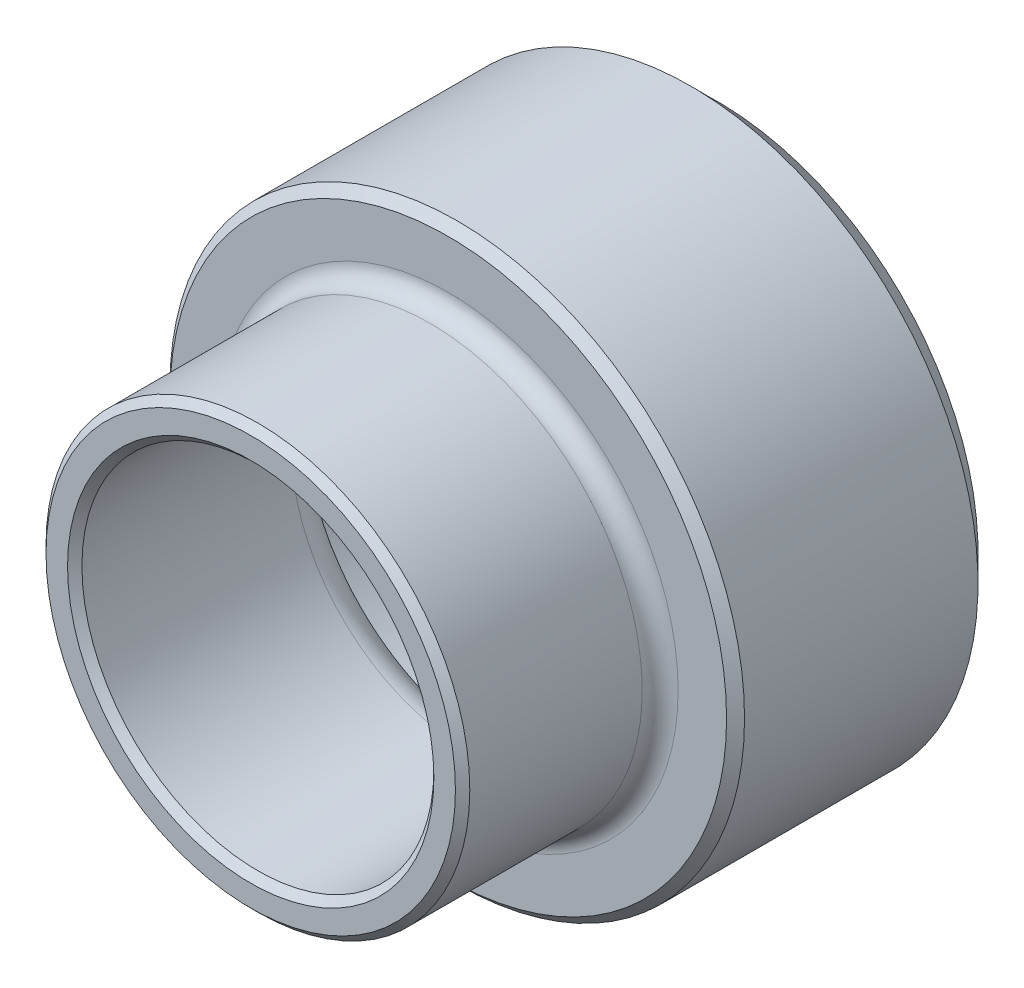
SolidWorks part; units mm, degrees
material "Brass"
ref_plane "Front" through (0, 0, 0) normal (0, 0, 1) x (1, 0, 0)
ref_plane "Top" through (0, 0, 0) normal (0, 1, 0) x (1, 0, 0)
ref_plane "Right" through (0, 0, 0) normal (1, 0, 0) x (0, 0, -1)
ref_plane "Plane1" through (0, 0, 0) normal (0, -1, 0) x (1, 0, 0)
sketch "Sketch1" plane through (0, 0, 0) normal (0, -1, 0) x (1, 0, 0)
  line L0 (5.9, 13) -> (4.9, 13)
  line L1 (4.9, 13) -> (4.9, 5.75)
  line L2 (4.9, 5.75) -> (0, 5.75)
  line L3 (0, 5.75) -> (0, 0)
  line L4 (0, 0) -> (8, 0)
  line L5 (8, 0) -> (8, 7.5)
  line L6 (8, 7.5) -> (6.4, 7.5)
  line L7 (5.9, 8) -> (5.9, 13)
  line L8 (0, 13) -> (0, 0) construction
  line L10 (0, 5.75) -> (4.9, 5.75) construction
  line L11 (6.4, 7.5) -> (5.9, 7.5) construction
  line L12 (5.9, 7.5) -> (5.9, 8) construction
  line L14 (4.9, 5.75) -> (4.9, 0) construction
  line L15 (4.9, 13) -> (0, 13) construction
  arc A0 (6.4, 7.5) -> (5.9, 8) centre (6.4, 8) cw
  dimension "D9" = 0.5
  dimension "D1" = 11.8
  dimension "D2" = 9.8
  dimension "D3" = 16
  dimension "D4" = 5.75
  dimension "D7" = 13
  dimension "D8" = 5.5
revolve "Revolve1" add sketch "Sketch1" angle 360 about L8 reverse direction yes
hole_wizard "Ø12.0 (12) Diameter Hole1" positions "Sketch3" profile "Sketch2" hole size "Ø12.0" standard "ISO"
sketch "Sketch3" plane through (0, 0, 0) normal (0, 0, -1) x (-1, 0, 0)
  point P0 (0, 0)
sketch "Sketch2" plane through (0, 0, 0) normal (1, 0, 0) x (0, 1, 0)
  line L0 (0, 0) -> (0, 9.3552)
  line L1 (0, 9.3552) -> (6, 5.75)
  line L2 (6, 5.75) -> (6, 0)
  line L5 (6, 0) -> (0, 0)
  line L10 (0, 9.3552) -> (-6, 5.75) construction
  line L11 (0, -6.35) -> (0, 107.95) construction
  dimension "Hole Dia." = 12
  dimension "Hole Depth" = 5.75
  dimension "Drill Angle" = 118
chamfer "Chamfer1" distance 0.75 angle 45 1 edges at (-8, 0, 0)
chamfer "Chamfer2" distance 0.25 angle 45 1 edges at (-8, 0, 7.5)
chamfer "Chamfer3" distance 0.2 angle 45 3 edges at (-5.9, 0, 13) (-4.9, 0, 13) (-6, 0, 0)
fillet "Fillet1" radius 1 1 edges at (-4.9, 0, 6.4109)
